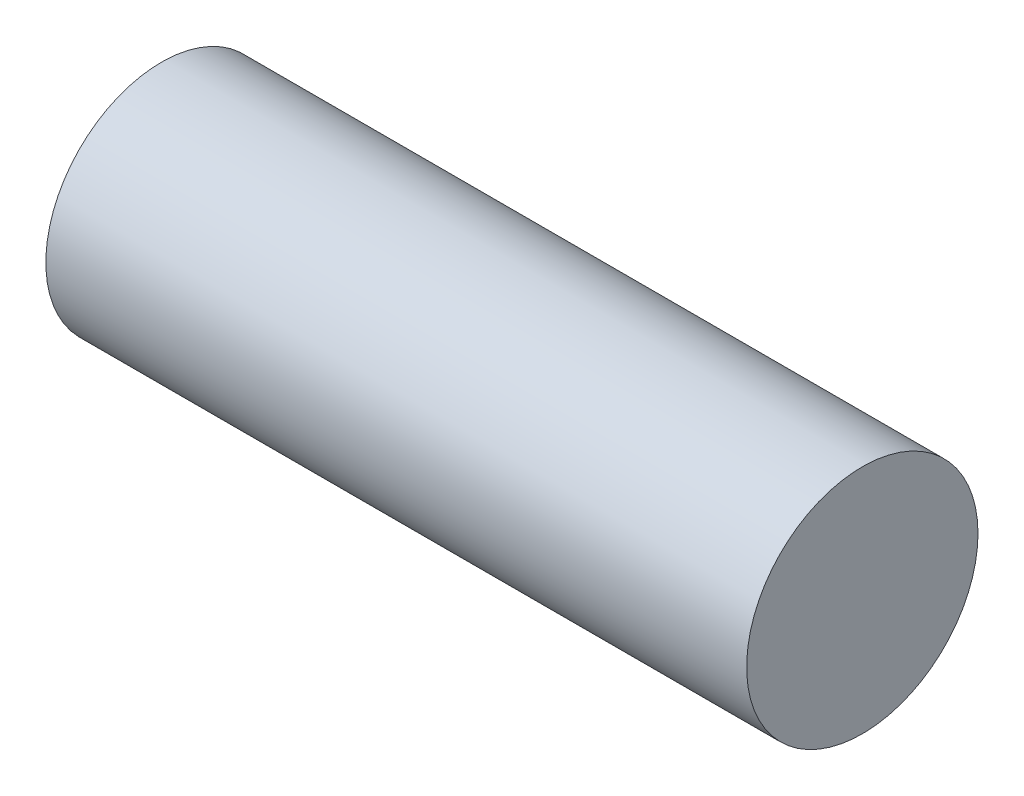
SolidWorks part; units mm, degrees
material "Chrome Stainless Steel"
ref_plane "Front Plane" through (0, 0, 0) normal (0, 0, 1) x (1, 0, 0)
ref_plane "Top Plane" through (0, 0, 0) normal (0, 1, 0) x (1, 0, 0)
ref_plane "Right Plane" through (0, 0, 0) normal (1, 0, 0) x (0, 0, -1)
other "Configuration Table"
sketch "Sketch1" plane through (0, 0, 0) normal (1, 0, 0) x (0, 0, -1)
  circle A0 centre (0, 0) radius 6
  dimension "D1" = 12
extrude "Boss-Extrude1" add sketch "Sketch1" along normal blind 36.35
ref_plane "Plane1" through (18.175, 0, 0) normal (1, 0, 0) x (0, 0, -1)
ref_axis "Axis1" through (36.35, 0, 0) along (-1, 0, 0)
